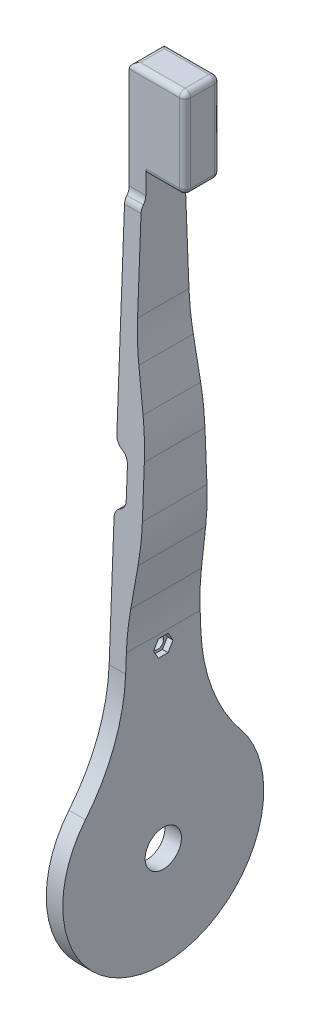
SolidWorks part; units mm, degrees
material "ABS"
ref_plane "Front Plane" through (0, 0, 0) normal (0, 0, 1) x (1, 0, 0)
ref_plane "Top Plane" through (0, 0, 0) normal (0, 1, 0) x (1, 0, 0)
ref_plane "Right Plane" through (0, 0, 0) normal (1, 0, 0) x (0, 0, -1)
sketch "Sketch2" plane through (0, 0, 0) normal (1, 0, 0) x (0, 0, -1)
  line L0 (4.9771, 193.675) -> (11.5599, 26.1323)
  line L1 (0, 193.675) -> (0, 28.575) construction
  line L2 (-4.9771, 193.675) -> (-11.5599, 26.1323)
  line L4 (-4.9771, 193.675) -> (4.9771, 193.675)
  circle A0 centre (0, 0) radius 28.575
  circle A1 centre (0, 0) radius 11.1125
  dimension "D1" = 57.15
  dimension "D5" = 22.225
  dimension "D2" = 11.5599
  dimension "D3" = 2.25
  dimension "D4" = 165.1
extrude "Boss-Extrude1" add sketch "Sketch2" against normal blind 6.35 contours A0 A1 region at (0, 15.1508, -23.269)
extrude "Boss-Extrude2" add sketch "Sketch2<5>" along normal blind 3.175 and the other way blind 1.524 contours L4 L1 A0 L0 | L1 L4 L2 A0 region at (0, 99.7845, -4.3525) region at (0, 99.7845, 4.3525)
sketch "Sketch2<5>" plane through (0, 0, 0) normal (1, 0, 0) x (0, 0, -1) same geometry as "Sketch2"
sketch "Sketch3" plane through (3.175, 0, 0) normal (1, 0, 0) x (0, 0, -1)
  line L0 (-4.9771, 193.675) -> (-4.9771, 168.275)
  line L1 (-4.9771, 168.275) -> (4.9771, 168.275)
  line L2 (4.9771, 168.275) -> (4.9771, 193.675)
  line L3 (-4.9771, 193.675) -> (4.9771, 193.675)
  dimension "D1" = 25.4
extrude "Boss-Extrude3" add sketch "Sketch3" along normal blind 11.176
sketch "Sketch4" plane through (3.175, 0, 0) normal (1, 0, 0) x (0, 0, -1)
  line L0 (-4.9771, 193.675) -> (-4.9771, 161.925)
  line L1 (-4.9771, 161.925) -> (-6.2246, 161.925)
  line L2 (-6.2246, 161.925) -> (-6.2246, 193.675)
  line L3 (-6.2246, 193.675) -> (-4.9771, 193.675)
  line L4 (-4.9771, 193.675) -> (-4.9086, 193.5806)
  line L5 (-4.9771, 193.675) -> (-11.5599, 26.1323) construction
  line L7 (0, 193.675) -> (0, 168.275) construction
  line L8 (-4.9771, 193.675) -> (4.9771, 193.675) construction
  line L9 (-4.9771, 168.275) -> (4.9771, 168.275) construction
  line L10 (4.9771, 193.675) -> (4.9086, 193.5806)
  line L11 (6.2246, 193.675) -> (4.9771, 193.675)
  line L12 (6.2246, 161.925) -> (6.2246, 193.675)
  line L13 (4.9771, 161.925) -> (6.2246, 161.925)
  line L14 (4.9771, 193.675) -> (4.9771, 161.925)
  line L15 (-4.9771, 168.275) -> (4.9771, 168.275) construction
  line M2 (4.9771, 193.675) -> (4.9771, 168.275)
  line M4 (-4.9771, 168.275) -> (-4.9771, 193.675)
  line M5 (-4.9771, 193.675) -> (-11.5599, 26.1323)
  line M7 (11.5599, 26.1323) -> (4.9771, 193.675)
  dimension "D1" = 6.35
extrude "Cut-Extrude1" cut sketch "Sketch4" against normal through all contours L1 M4 M5 | L13 M2 M7 region at (3.175, 172.5083, 5.3929) region at (3.175, 172.5083, -5.3929)
fillet "Fillet2" radius 3.175 2 edges at (0.8255, 161.925, 6.2246) (0.8255, 161.925, -6.2246)
fillet "Fillet4" radius 3.175 2 edges at (0.8255, 161.925, 4.9771) (0.8255, 161.925, -4.9771)
fillet "Fillet7" radius 1.5875 9 edges at (8.763, 168.275, 4.9771) (8.763, 168.275, -4.9771) (14.351, 180.975, -4.9771) (6.4135, 193.675, 4.9771) (14.351, 180.975, 4.9771) (-1.524, 193.675, 0) (14.351, 193.675, 0) (14.351, 168.275, 0) (6.4135, 193.675, -4.9771)
sketch "Sketch5" plane through (0, 0, 0) normal (1, 0, 0) x (0, 0, -1)
  circle A1 centre (0, 0) radius 28.575
  dimension "D1" = 57.15
extrude "Cut-Extrude2" cut sketch "Sketch5" against normal through all
sketch "Sketch6" plane through (3.175, 0, 0) normal (1, 0, 0) x (0, 0, -1)
  circle A0 centre (0, 0) radius 28.575
  arc A1 (11.5599, 26.1323) -> (-11.5599, 26.1323) centre (0, 0) ccw construction
extrude "Boss-Extrude4" add sketch "Sketch6" against normal up to surface (4.699 mm away) up to face at (-1.524, 140.683, 0)
hole_wizard "3/8 Clearance Hole1" positions "Sketch8" profile "Sketch7" hole size "3/8" standard "ANSI Inch" end condition through all
sketch "Sketch8" plane through (3.175, 0, 0) normal (1, 0, 0) x (0, 0, -1)
  point P0 (0, 0)
sketch "Sketch7" plane through (3.175, 0, 0) normal (0, 1, 0) x (0, 0, -1)
  line L0 (0, 0) -> (0, 4.699)
  line L1 (0, 4.699) -> (5.1587, 4.699)
  line L2 (5.1587, 4.699) -> (5.1587, 0)
  line L5 (5.1587, 0) -> (0, 0)
  line L11 (0, -6.35) -> (0, 107.95) construction
  dimension "Thru Hole Dia." = 10.3175
  dimension "Thru Hole Depth" = 4.699
fillet "Fillet9" radius 50.8 2 edges at (0.8255, 26.1323, 11.5599) (0.8255, 26.1323, -11.5599)
hole_wizard "#4 Clearance Hole1" positions "Sketch10" profile "Sketch9" hole size "#4" standard "ANSI Inch" end condition through all
sketch "Sketch10" plane through (3.175, 0, 0) normal (1, 0, 0) x (0, 0, -1)
  line L0 (-10.6266, 49.8873) -> (10.6266, 49.8873) construction
  line L1 (-6.3217, 159.4537) -> (-10.6911, 48.2456) construction
  line L2 (6.3217, 159.4537) -> (10.6911, 48.2456) construction
  line L5 (3.3896, 192.0875) -> (-3.3896, 192.0875) construction
  line L6 (65.0064, 32.4689) -> (0, 49.8873) construction
  line L7 (59.9587, -55.5099) -> (-83.6938, -17.0183) construction
  point P0 (0, 49.8873)
sketch "Sketch9" plane through (3.175, 49.8873, 0) normal (0, 1, 0) x (0, 0, -1)
  line L0 (0, 0) -> (0, 4.699)
  line L1 (0, 4.699) -> (1.7272, 4.699)
  line L2 (1.7272, 4.699) -> (1.7272, 0)
  line L5 (1.7272, 0) -> (0, 0)
  line L11 (0, -6.35) -> (0, 107.95) construction
  dimension "Thru Hole Dia." = 3.4544
  dimension "Thru Hole Depth" = 4.699
sketch "Sketch11" plane through (3.175, 0, 0) normal (1, 0, 0) x (0, 0, -1)
  line L0 (-1.3823, 47.493) -> (1.3823, 47.493)
  line L1 (-1.2357, 47.747) -> (1.2357, 47.747) construction
  line L2 (1.2357, 47.747) -> (2.4714, 49.8873) construction
  line L3 (2.4714, 49.8873) -> (1.2357, 52.0276) construction
  line L4 (1.2357, 52.0276) -> (-1.2357, 52.0276) construction
  line L5 (-1.2357, 52.0276) -> (-2.4714, 49.8873) construction
  line L6 (-2.4714, 49.8873) -> (-1.2357, 47.747) construction
  line L7 (1.3823, 47.493) -> (2.7647, 49.8873)
  line L8 (2.7647, 49.8873) -> (1.3823, 52.2816)
  line L9 (1.3823, 52.2816) -> (-1.3823, 52.2816)
  line L10 (-1.3823, 52.2816) -> (-2.7647, 49.8873)
  line L11 (-2.7647, 49.8873) -> (-1.3823, 47.493)
  line L12 (3.3896, 192.0875) -> (-3.3896, 192.0875) construction
  circle A0 centre (0, 49.8873) radius 2.1403 construction
  dimension "D1" = 0.254
extrude "Cut-Extrude3" cut sketch "Sketch11" against normal blind 1.6002
sketch "Sketch12" plane through (3.175, 0, 0) normal (1, 0, 0) x (0, 0, -1)
  line L0 (0.0633, -0.0824) -> (0.0633, 151.2674) construction
  circle A1 centre (0.0633, -0.0824) radius 93.8714 construction
  point P2 (0.0633, 93.7889)
sketch "Sketch13" plane through (3.175, 0, 0) normal (1, 0, 0) x (0, 0, -1)
  line L0 (6.3217, 159.4537) -> (10.6911, 48.2456) construction
  line L1 (-6.3217, 159.4537) -> (-10.6911, 48.2456) construction
  line L2 (8.4027, 106.4889) -> (9.4006, 81.0889)
  line L3 (-8.4027, 106.4889) -> (-9.4006, 81.0889)
  line L4 (-8.4027, 106.4889) -> (8.4027, 106.4889)
  line L5 (-9.4006, 81.0889) -> (9.4006, 81.0889)
  dimension "D1" = 12.7
  dimension "D2" = 25.4
extrude "Boss-Extrude5" add sketch "Sketch13" along normal offset from surface (3.2385 mm away) 7.9375 up to face at (-1.524, 49.8873, -1.7272)
sketch "Sketch14" plane through (0, 0, 0) normal (0, 0, 1) x (1, 0, 0)
  line L0 (-1.524, 101.7899) -> (1.7145, 100.1389)
  line L2 (1.7145, 100.1389) -> (1.7145, 87.4389)
  line L3 (1.7145, 93.7889) -> (3.175, 93.7889) construction
  line L4 (6.4135, 106.4889) -> (6.4135, 81.0889) construction
  line L5 (-1.524, 159.4537) -> (-1.524, 48.2456) construction
  line L7 (6.4135, 106.4889) -> (3.175, 106.4889) construction
  line L8 (-1.524, 101.7899) -> (-1.524, 85.7879)
  line L9 (-1.524, 85.7879) -> (1.7145, 87.4389)
  point P15 (-1.524, 93.7889)
  dimension "D1" = 4.699
  dimension "D2" = 4.699
  dimension "D3" = 6.35
extrude "Cut-Extrude4" cut sketch "Sketch14" against normal through all both and the other way through all
sketch "Sketch15" plane through (0, 0.4938, 12.5672) normal (0, 0.0393, 0.9992) x (1, 0, 0)
  line L0 (3.175, 80.6573) -> (3.175, 47.7887) construction
  line L1 (6.4135, 80.6573) -> (3.175, 80.6573) construction
  line L2 (6.4135, 106.0769) -> (3.175, 106.0769) construction
  line L3 (3.175, 159.0826) -> (3.175, 106.0769) construction
  line L4 (3.175, 80.6573) -> (3.175, 58.4323)
  line L5 (6.4135, 80.6573) -> (3.175, 80.6573)
  line L6 (6.4135, 106.0769) -> (3.175, 106.0769)
  line L7 (3.175, 128.3019) -> (3.175, 106.0769)
  line L8 (6.4135, 106.0769) -> (3.175, 128.3019)
  line L9 (6.4135, 80.6573) -> (3.175, 58.4323)
  dimension "D1" = 22.225
extrude "Boss-Extrude6" add sketch "Sketch15" along direction (0, 0, 1) on the side against the normal up to surface (20.5464 mm away) up to face at (1.905, 97.1425, -8.7699)
fillet "Fillet16" radius 3.175 2 edges at (1.7145, 100.1389, 0) (1.7145, 87.4389, 0)
fillet "Fillet17" radius 3.175 2 edges at (-1.524, 101.7899, 0) (-1.524, 85.7879, 0)
fillet "Fillet18" radius 76.2 4 edges at (3.175, 128.6968, 0) (6.4135, 106.4889, 0) (6.4135, 81.0889, 0) (3.175, 58.8811, 0)
